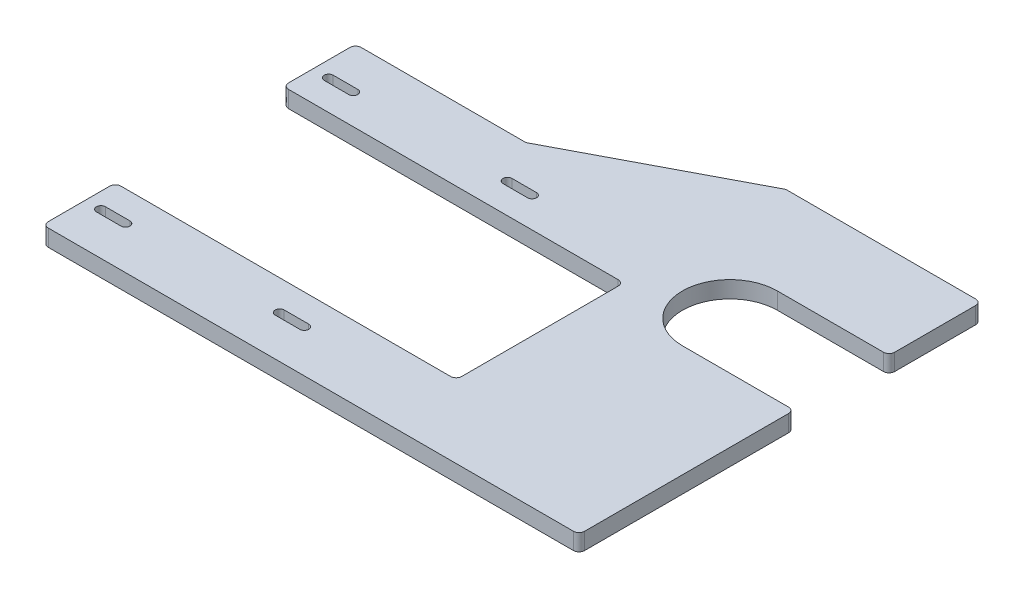
SolidWorks part; units mm, degrees
material "PC High Viscosity"
ref_plane "Front Plane" through (0, 0, 0) normal (0, 0, 1) x (1, 0, 0)
ref_plane "Top Plane" through (0, 0, 0) normal (0, 1, 0) x (1, 0, 0)
ref_plane "Right Plane" through (0, 0, 0) normal (1, 0, 0) x (0, 0, -1)
sketch "Sketch1" plane through (0, 0, 0) normal (0, 1, 0) x (1, 0, 0)
  line L0 (291.0488, 149.225) -> (241.3, 149.225) construction
  line L1 (0, 0) -> (304.8, 0)
  line L2 (0, 0) -> (0, 41.275)
  line L3 (0, 177.8) -> (96.8473, 177.8)
  line L4 (304.8, 0) -> (304.8, 122.2375)
  line L5 (304.8, 176.2125) -> (241.3, 176.2125)
  line L6 (304.8, 122.2375) -> (241.3, 122.2375)
  line L8 (0, 88.9) -> (58.6308, 88.9) construction
  line L9 (0, 136.525) -> (193.6945, 136.525)
  line L11 (0, 41.275) -> (193.6945, 41.275)
  line L12 (193.6945, 136.525) -> (193.6945, 41.275)
  line L13 (0, 136.525) -> (0, 177.8)
  line L14 (193.6945, 228.6) -> (96.8473, 177.8)
  line L17 (193.6945, 228.6) -> (304.8, 228.6)
  line L18 (304.8, 176.2125) -> (304.8, 228.6)
  arc A0 (241.3, 176.2125) -> (241.3, 122.2375) centre (241.3, 149.225) ccw
  dimension "D3" = 53.975
  dimension "D1" = 304.8
  dimension "D2" = 177.8
  dimension "D4" = 63.5
  dimension "D5" = 95.25
  dimension "D6" = 88.9
  dimension "D7" = 149.225
  dimension "D8" = 47.6055
  dimension "D9" = 228.6
extrude "Boss-Extrude1" add sketch "Sketch1" along normal blind 9.525
hole_wizard "#7 (0.201) Diameter Slot1" positions "Sketch2" profile "Sketch3" size "#7" standard "ANSI Inch" slot yes end condition through all
sketch "Sketch2" plane through (0, 9.525, 0) normal (0, 1, 0) x (1, 0, 0)
  line L0 (107.9695, 24.1711) -> (127.0195, 24.1711) construction
  line L1 (0, 0) -> (304.8, 0) construction
  line L2 (0, 41.275) -> (0, 0) construction
  line L3 (96.8473, 177.8) -> (0, 177.8) construction
  point P0 (117.4945, 24.1711)
  point P4 (15.8945, 24.1711)
  point P6 (117.4945, 153.6289)
  point P8 (15.8945, 153.6289)
  point P15 (0, 0)
  point P16 (0, 0)
  point P17 (0, 0)
  point P18 (0, 0)
  dimension "D1" = 19.05
  dimension "D2" = 24.1711
  dimension "D3" = 101.6
  dimension "D4" = 15.8945
  dimension "D5" = 24.1711
sketch "Sketch3" plane through (117.4945, 9.525, -24.1711) normal (1, 0, 0) x (0, 0, 1)
  line L0 (0, 0) -> (0, 9.525)
  line L1 (0, 9.525) -> (2.5527, 9.525)
  line L2 (2.5527, 9.525) -> (2.5527, 0)
  line L5 (2.5527, 0) -> (0, 0)
  line L11 (0, -6.35) -> (0, 107.95) construction
  dimension "Thru Hole Dia." = 5.1054
  dimension "Thru Hole Depth" = 9.525
fillet "Fillet1" radius 3.175 12 edges at (304.8, 4.7625, -176.2125) (304.8, 4.7625, -122.2375) (304.8, 4.7625, -228.6) (193.6945, 4.7625, -228.6) (96.8473, 4.7625, -177.8) (193.6945, 4.7625, -41.275) (193.6945, 4.7625, -136.525) (0, 4.7625, -177.8) (0, 4.7625, -136.525) (0, 4.7625, -41.275) (0, 4.7625, 0) (304.8, 4.7625, 0)
equation "\"D6@Sketch1\"=\"D2@Sketch1\"/2"
